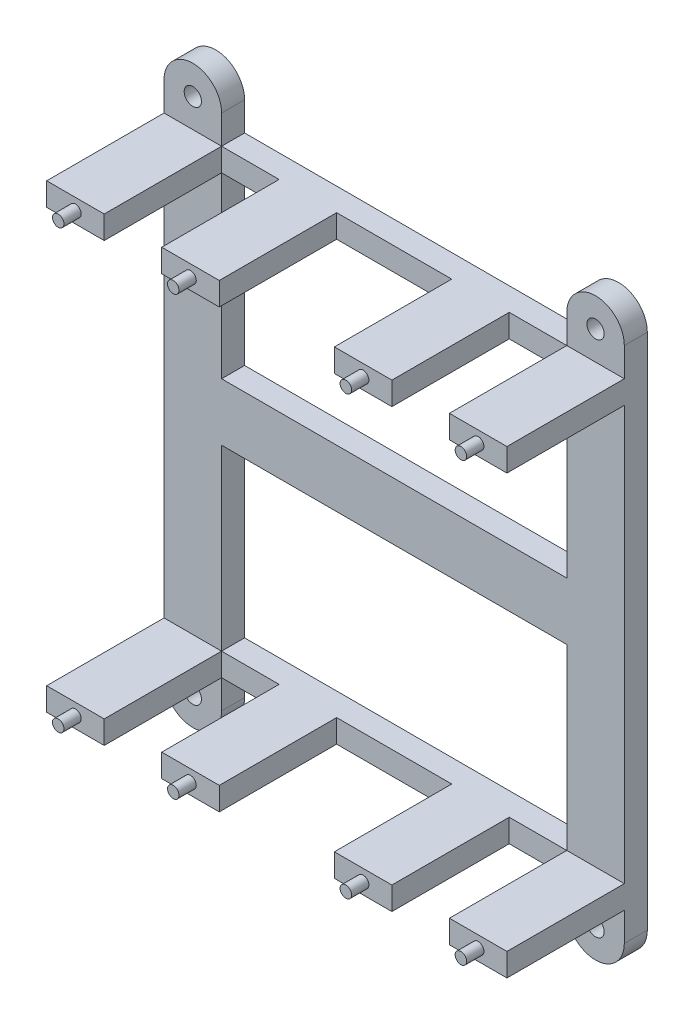
SolidWorks part; units mm, degrees
ref_plane "Alzado" through (0, 0, 0) normal (0, 0, 1) x (1, 0, 0)
ref_plane "Planta" through (0, 0, 0) normal (0, 1, 0) x (1, 0, 0)
ref_plane "Vista lateral" through (0, 0, 0) normal (1, 0, 0) x (0, 0, -1)
sketch "Croquis1" plane through (0, 0, 0) normal (0, 0, 1) x (1, 0, 0)
  line L0 (-50.9465, -21.9298) -> (-50.9465, -17.9298) construction
  line L1 (-50.9465, 58.0702) -> (29.0535, 58.0702)
  line L2 (-50.9465, 58.0702) -> (-50.9465, -21.9298)
  line L3 (-50.9465, -21.9298) -> (29.0535, -21.9298)
  line L4 (29.0535, 58.0702) -> (29.0535, -21.9298)
  line L5 (-50.9465, 58.0702) -> (-50.9465, 54.0702) construction
  line L6 (29.0535, -21.9298) -> (19.0535, -21.9298) construction
  line L7 (-50.9465, -17.9298) -> (29.0535, -17.9298)
  line L8 (-50.9465, -17.9298) -> (-50.9465, -21.9298)
  line L9 (-50.9465, -21.9298) -> (29.0535, -21.9298)
  line L10 (29.0535, -17.9298) -> (29.0535, -21.9298)
  line L11 (-50.9465, 54.0702) -> (29.0535, 54.0702)
  line L12 (-50.9465, 54.0702) -> (-50.9465, 58.0702)
  line L13 (-50.9465, 58.0702) -> (29.0535, 58.0702)
  line L14 (29.0535, 54.0702) -> (29.0535, 58.0702)
  line L15 (-50.9465, -21.9298) -> (-40.9465, -21.9298) construction
  line L16 (-50.9465, 18.0702) -> (29.0535, 18.0702) construction
  line L17 (29.0535, -21.9298) -> (19.0535, -21.9298)
  line L18 (29.0535, -21.9298) -> (29.0535, 58.0702)
  line L19 (29.0535, 58.0702) -> (19.0535, 58.0702)
  line L20 (19.0535, -21.9298) -> (19.0535, 58.0702)
  line L21 (-50.9465, 58.0702) -> (-40.9465, 58.0702)
  line L22 (-50.9465, 58.0702) -> (-50.9465, -21.9298)
  line L23 (-50.9465, -21.9298) -> (-40.9465, -21.9298)
  line L24 (-40.9465, 58.0702) -> (-40.9465, -21.9298)
  line L29 (19.0535, -21.9298) -> (9.5535, -21.9298) construction
  line L30 (29.0535, 18.0702) -> (29.0535, -6.4298) construction
  line L31 (29.0535, 18.0702) -> (29.0535, 42.5702) construction
  line L32 (29.0535, 42.5702) -> (-50.9465, 42.5702) construction
  line L33 (29.0535, -6.4298) -> (-50.9465, -6.4298) construction
  line L34 (29.0535, -6.4298) -> (26.0535, -6.4298) construction
  line L35 (-50.9465, 18.0702) -> (-50.9465, 43.0702) construction
  line L36 (-50.9465, 18.0702) -> (-50.9465, -6.9298) construction
  line L37 (-50.9465, 18.0702) -> (-50.9465, 49.0702) construction
  line L38 (-50.9465, 18.0702) -> (-50.9465, -12.9298) construction
  line L39 (-50.9465, 49.0702) -> (29.0535, 49.0702) construction
  line L40 (-50.9465, -12.9298) -> (29.0535, -12.9298) construction
  line L41 (9.5535, -21.9298) -> (9.5535, 58.0702) construction
  line L42 (9.5535, -12.9298) -> (-47.4465, -12.9298) construction
  line L43 (-47.4465, -21.9298) -> (-47.4465, 58.0702) construction
  line L44 (26.0535, -21.9298) -> (26.0535, 58.0702) construction
  line L45 (-50.9465, 43.0702) -> (29.0535, 43.0702) construction
  line L46 (-50.9465, -6.9298) -> (29.0535, -6.9298) construction
  line L47 (26.0535, -6.4298) -> (-31.9465, -6.4298) construction
  line L48 (-40.9465, 58.0702) -> (-40.9465, 68.0702) construction
  line L49 (-40.9465, -21.9298) -> (-40.9465, -31.9298) construction
  line L50 (-50.9465, -21.9298) -> (-40.9465, -31.9298) construction
  line L51 (-50.9465, -21.9298) -> (-40.9465, -21.9298)
  line L52 (-50.9465, -21.9298) -> (-50.9465, -31.9298)
  line L53 (-50.9465, -31.9298) -> (-40.9465, -31.9298)
  line L54 (-40.9465, -21.9298) -> (-40.9465, -31.9298)
  line L55 (19.0535, -21.9298) -> (29.0535, -21.9298)
  line L56 (19.0535, -21.9298) -> (19.0535, -31.9298)
  line L57 (19.0535, -31.9298) -> (29.0535, -31.9298)
  line L58 (29.0535, -21.9298) -> (29.0535, -31.9298)
  line L59 (-50.9465, 58.0702) -> (-40.9465, 58.0702)
  line L60 (-50.9465, 58.0702) -> (-50.9465, 68.0702)
  line L61 (-50.9465, 68.0702) -> (-40.9465, 68.0702)
  line L62 (-40.9465, 58.0702) -> (-40.9465, 68.0702)
  line L63 (19.0535, 58.0702) -> (29.0535, 58.0702)
  line L64 (19.0535, 58.0702) -> (19.0535, 68.0702)
  line L65 (19.0535, 68.0702) -> (29.0535, 68.0702)
  line L66 (29.0535, 58.0702) -> (29.0535, 68.0702)
  line L67 (-50.9465, -31.9298) -> (-40.9465, -21.9298) construction
  line L68 (19.0535, -21.9298) -> (29.0535, -31.9298) construction
  line L69 (19.0535, -31.9298) -> (29.0535, -21.9298) construction
  line L70 (19.0535, 68.0702) -> (29.0535, 58.0702) construction
  line L71 (29.0535, 68.0702) -> (19.0535, 58.0702) construction
  line L72 (-50.9465, 58.0702) -> (-40.9465, 68.0702) construction
  line L73 (-40.9465, 58.0702) -> (-50.9465, 68.0702) construction
  line L74 (-10.9465, 58.0702) -> (-10.9465, -21.9298)
  line L75 (-30.9465, 58.0702) -> (-30.9465, -21.9298)
  line L76 (9.0535, 58.0702) -> (9.0535, -21.9298)
  line L77 (-20.9465, 58.0702) -> (-20.9465, -21.9298)
  line L78 (-0.9465, 58.0702) -> (-0.9465, -21.9298)
  line L79 (-50.9465, 13.0702) -> (29.0535, 13.0702)
  line L80 (-50.9465, 23.0702) -> (29.0535, 23.0702)
  line L82 (-50.9465, 13.0702) -> (29.0535, 13.0702)
  line L83 (-50.9465, 13.0702) -> (-50.9465, 23.0702)
  line L84 (-50.9465, 23.0702) -> (29.0535, 23.0702)
  line L85 (29.0535, 13.0702) -> (29.0535, 23.0702)
  line L86 (-50.9465, -21.9298) -> (29.0535, -21.9298)
  line L87 (-50.9465, -21.9298) -> (-50.9465, -17.9298)
  line L88 (-50.9465, -17.9298) -> (29.0535, -17.9298)
  line L89 (29.0535, -21.9298) -> (29.0535, -17.9298)
  line L90 (-50.9465, 54.0702) -> (29.0535, 54.0702)
  line L91 (-50.9465, 54.0702) -> (-50.9465, 58.0702)
  line L92 (-50.9465, 58.0702) -> (29.0535, 58.0702)
  line L93 (29.0535, 54.0702) -> (29.0535, 58.0702)
  circle A0 centre (9.5535, -12.9298) radius 3.5
  circle A1 centre (9.5535, 49.0702) radius 3.5
  circle A2 centre (9.5535, 49.0702) radius 1.5
  circle A3 centre (9.5535, -12.9298) radius 1.5
  circle A4 centre (9.5535, 49.0702) radius 2.2
  circle A5 centre (9.5535, -12.9298) radius 2.2
  circle A12 centre (26.0535, 42.5702) radius 3
  circle A13 centre (26.0535, -6.4298) radius 3
  circle A14 centre (-47.4465, 43.0702) radius 3.5
  circle A15 centre (-47.4465, 43.0702) radius 2.2
  circle A16 centre (-47.4465, 43.0702) radius 1.5
  circle A17 centre (-47.4465, -6.9298) radius 3.5
  circle A18 centre (-47.4465, -6.9298) radius 2.2
  circle A19 centre (-47.4465, -6.9298) radius 1.5
  circle A20 centre (26.0535, -6.4298) radius 1.25
  circle A21 centre (26.0535, 42.5702) radius 1.25
  circle A22 centre (-31.9465, -6.4298) radius 3
  circle A23 centre (-31.9465, -6.4298) radius 1.25
  circle A24 centre (-31.9465, 42.5702) radius 3
  circle A25 centre (-31.9465, 42.5702) radius 1.25
  circle A26 centre (-45.9465, 63.0702) radius 1.5
  circle A27 centre (24.0535, 63.0702) radius 1.5
  circle A28 centre (24.0535, -26.9298) radius 1.5
  circle A29 centre (-45.9465, -26.9298) radius 1.5
  dimension "D15" = 57
  dimension "D16" = 58
  dimension "D19" = 20
  dimension "D1" = 80
  dimension "D2" = 80
  dimension "D3" = 4
  dimension "D4" = 4
  dimension "D5" = 10
  dimension "D6" = 10
  dimension "D7" = 9.5
  dimension "D8" = 24.5
  dimension "D9" = 24.5
  dimension "D10" = 3
  dimension "D11" = 25
  dimension "D12" = 25
  dimension "D13" = 31
  dimension "D14" = 31
  dimension "D20" = 20
  dimension "D21" = 10
  dimension "D22" = 10
  dimension "D23" = 5
  dimension "D24" = 5
extrude "Saliente-Extruir5" add sketch "Croquis1" along normal blind 4 contours L1 L62 L61 L60 A26 | L13 L66 L65 L64 A27 | L58 L9 L56 L57 A28 | L54 L3 L52 L53 A29 | L24 L7 L2 L3 | L75 L7 L24 L9 | L77 L7 L75 L3 | L7 L77 L9 L74 | L78 L7 L74 L3 | L7 L78 L9 L76 | L7 L76 L9 L20 | L20 L9 L4 L7 | A13 A20 | A20 | L4 A13 L18 L79 L20 L7 | L22 A17 L2 L7 L24 L79 | A17 A18 | A18 A19 | A19 | L80 L22 L79 L24 | L80 L24 L79 L75 | L80 L75 L79 L77 | L80 L77 L79 L74 | L80 L74 L79 L78 | L80 L78 L79 L76 | L80 L76 L79 L20 | L80 L20 L79 L18 | L2 A14 L22 L80 L24 L11 | L24 L1 L2 L11 | A14 A15 | A15 A16 | A16 | L75 L13 L24 L11 | L77 L1 L75 L11 | L13 L77 L11 L74 | L78 L1 L74 L11 | L13 L78 L11 L76 | L13 L76 L11 L20 | L20 L11 L4 L13 | L18 A12 L4 L11 L20 L80 | A12 A21 | A21 region at (-50.8051, 63.0702, 0) region at (-45.9465, 56.0702, 0) region at (-35.9465, 56.0702, 0) region at (-47.4465, 46.4712, 0) region at (-45.7339, 37.9323, 0) region at (-25.9465, 56.0702, 0) region at (-15.9465, 56.0702, 0) region at (-35.9465, 18.0702, 0) region at (-45.9465, 18.0702, 0) region at (-5.9465, 56.0702, 0) region at (-47.4465, -3.5288, 0) region at (-45.7339, -1.792, 0) region at (-25.9465, 18.0702, 0) region at (4.0535, 56.0702, 0) region at (-15.9465, 18.0702, 0) region at (-45.9465, -19.9298, 0) region at (-35.9465, -19.9298, 0) region at (14.0535, 56.0702, 0) region at (-5.9465, 18.0702, 0) region at (-25.9465, -19.9298, 0) region at (-41.0879, -26.9298, 0) region at (19.1949, 63.0702, 0) region at (24.0535, 56.0702, 0) region at (4.0535, 18.0702, 0) region at (-15.9465, -19.9298, 0) region at (23.1383, 42.5702, 0) region at (23.8528, 38.1687, 0) region at (14.0535, 18.0702, 0) region at (-5.9465, -19.9298, 0) region at (24.0535, 18.0702, 0) region at (4.0535, -19.9298, 0) region at (23.1383, -6.4298, 0) region at (23.8528, -2.0284, 0) region at (14.0535, -19.9298, 0) region at (24.0535, -19.9298, 0) region at (24.0535, -22.0712, 0) region at (-49.5843, 43.0702, 0) region at (-47.4465, 43.0702, 0) region at (-49.5843, -6.9298, 0) region at (-47.4465, -6.9298, 0) region at (26.0535, -6.4298, 0) region at (26.0535, 42.5702, 0)
extrude "Saliente-Extruir6" add sketch "Croquis1<6>" along normal blind 20.4 from surface contours L24 L1 L2 L11 | L77 L1 L75 L11 | L20 L11 L4 L13 | L13 L78 L11 L76 | L24 L7 L2 L3 | L77 L7 L75 L3 | L7 L78 L9 L76 | L20 L9 L4 L7 region at (-45.9465, 56.0702, 0) region at (-25.9465, 56.0702, 0) region at (4.0535, 56.0702, 0) region at (-45.9465, -19.9298, 0) region at (-25.9465, -19.9298, 0) region at (24.0535, 56.0702, 0) region at (4.0535, -19.9298, 0) region at (24.0535, -19.9298, 0) starting at face at (-10.9465, -2.4298, 4)
sketch "Croquis1<6>" plane through (0, 0, 0) normal (0, 0, 1) x (1, 0, 0) same geometry as "Croquis1"
extrude "Saliente-Extruir7" add sketch "Croquis1<7>" along normal blind 4 from surface contours L24 L1 L2 L11 | L75 L13 L24 L11 | L13 L77 L11 L74 | L78 L1 L74 L11 | L13 L78 L11 L76 | L77 L1 L75 L11 | L13 L76 L11 L20 | L18 A12 L4 L11 L20 L80 | L2 A14 L22 L80 L24 L11 | A24 L75 L11 L24 L80 | A14 A15 | A15 A16 | A16 | A12 A21 | A21 | L20 L11 L4 L13 | A25 L75 A24 | L75 A25 | A25 L75 A24 | L75 A25 | A24 L75 L80 L77 L11 | L77 L80 L74 L11 | L74 L80 L78 L11 | A1 L76 L11 L78 L80 | A4 L76 A1 | L76 A4 A2 | L76 A2 | L76 A2 | L76 A4 A2 | A4 L76 A1 | A1 L76 L80 L20 L11 | L80 L20 L79 L18 | L80 L76 L79 L20 | L80 L78 L79 L76 | L80 L74 L79 L78 | L80 L77 L79 L74 | L80 L75 L79 L77 | L80 L24 L79 L75 | L80 L22 L79 L24 | A22 L75 L79 L24 L7 | A22 L75 L7 L77 L79 | L79 L77 L7 L74 | L79 L74 L7 L78 | A0 L76 L79 L78 L7 | A0 L76 L7 L20 L79 | L22 A17 L2 L7 L24 L79 | A17 A18 | A18 A19 | A19 | A23 L75 A22 | L75 A23 | L75 A23 | A23 L75 A22 | A13 A20 | A20 | L76 A3 | L76 A3 | L76 A5 A3 | A5 L76 A0 | L76 A5 A3 | A5 L76 A0 | L20 L9 L4 L7 | L7 L76 L9 L20 | L7 L78 L9 L76 | L78 L7 L74 L3 | L7 L77 L9 L74 | L77 L7 L75 L3 | L75 L7 L24 L9 | L24 L7 L2 L3 | L4 A13 L18 L79 L20 L7 region at (-45.9465, 56.0702, 0) region at (-35.9465, 56.0702, 0) region at (-47.4465, 46.4712, 0) region at (-45.7339, 37.9323, 0) region at (-25.9465, 56.0702, 0) region at (-36.1707, 38.294, 0) region at (-15.9465, 56.0702, 0) region at (-25.8325, 38.4608, 0) region at (-35.9465, 18.0702, 0) region at (-45.9465, 18.0702, 0) region at (-5.9465, 56.0702, 0) region at (-15.9465, 38.5702, 0) region at (-30.0948, 42.5702, 0) region at (-31.0186, 44.3594, 0) region at (-36.1707, -2.1536, 0) region at (-47.4465, -3.5288, 0) region at (-45.7339, -1.792, 0) region at (-25.9465, 18.0702, 0) region at (4.0535, 56.0702, 0) region at (-5.9465, 38.5702, 0) region at (-15.9465, 18.0702, 0) region at (-30.8456, 42.5702, 0) region at (-32.007, 42.5702, 0) region at (-45.9465, -19.9298, 0) region at (-35.9465, -19.9298, 0) region at (-25.8325, -2.3205, 0) region at (14.0535, 56.0702, 0) region at (3.8532, 38.008, 0) region at (-5.9465, 18.0702, 0) region at (-15.9465, -2.4298, 0) region at (-25.9465, -19.9298, 0) region at (-30.0948, -6.4298, 0) region at (-31.0186, -4.6406, 0) region at (24.0535, 56.0702, 0) region at (14.3131, 37.7394, 0) region at (4.0535, 18.0702, 0) region at (-5.9465, -2.4298, 0) region at (-15.9465, -19.9298, 0) region at (-30.8456, -6.4298, 0) region at (-32.007, -6.4298, 0) region at (23.1383, 42.5702, 0) region at (23.8528, 38.1687, 0) region at (11.792, 51.655, 0) region at (8.978, 51.8734, 0) region at (3.8532, -1.8676, 0) region at (14.0535, 18.0702, 0) region at (-5.9465, -19.9298, 0) region at (24.0535, 18.0702, 0) region at (10.8889, 50.7531, 0) region at (9.0074, 50.8485, 0) region at (4.0535, -19.9298, 0) region at (14.3131, -1.599, 0) region at (23.1383, -6.4298, 0) region at (23.8528, -2.0284, 0) region at (9.9301, 49.0702, 0) region at (8.6393, 49.0702, 0) region at (14.0535, -19.9298, 0) region at (11.792, -10.345, 0) region at (8.978, -10.1266, 0) region at (24.0535, -19.9298, 0)
sketch "Croquis1<7>" plane through (0, 0, 0) normal (0, 0, 1) x (1, 0, 0) same geometry as "Croquis1"
extrude "Saliente-Extruir9" add sketch "Croquis1<10>" along normal blind 4 from surface contours A24 | A12 | A13 | A22 starting at face at (-10.9465, 18.0702, 28.4)
sketch "Croquis1<10>" plane through (0, 0, 0) normal (0, 0, 1) x (1, 0, 0) same geometry as "Croquis1"
extrude "Saliente-Extruir10" add sketch "Croquis1<11>" along normal blind 14 from surface contours A14 | A17 | A0 | A1 starting at face at (-34.9465, -6.4298, 28.4)
sketch "Croquis1<11>" plane through (0, 0, 0) normal (0, 0, 1) x (1, 0, 0) same geometry as "Croquis1"
extrude "Cortar-Extruir1" cut sketch "Croquis1<12>" against normal blind 14 and the other way blind 14 from surface contours A19 | A23 | A3 | A20 | A21 | A2 | A25 | A16 starting at face at (6.0535, 49.0702, 28.4)
sketch "Croquis1<12>" plane through (0, 0, 0) normal (0, 0, 1) x (1, 0, 0) same geometry as "Croquis1"
extrude "Cortar-Extruir2" cut sketch "Croquis1<13>" along normal blind 15 from surface contours A5 | A18 | A15 | A4 starting at face at (-33.1965, -6.4298, 24.4)
sketch "Croquis1<13>" plane through (0, 0, 0) normal (0, 0, 1) x (1, 0, 0) same geometry as "Croquis1"
fillet "Redondeo2" 2 edges at (-40.9465, 68.0702, 2) (-50.9465, 68.0702, 2) type full round first side face at (-40.9465, 63.0702, 2) second side face at (-50.9465, 18.0702, 12.96) middle face at (-45.9465, 68.0702, 2)
fillet "Redondeo3" 2 edges at (-50.9465, -31.9298, 2) (-40.9465, -31.9298, 2) type full round first side face at (-50.9465, 17.0702, 12.96) second side face at (-40.9465, -26.9298, 2) middle face at (-45.9465, -31.9298, 2)
fillet "Redondeo4" 2 edges at (19.0535, -31.9298, 2) (29.0535, -31.9298, 2) type full round first side face at (19.0535, -26.9298, 2) second side face at (29.0535, 18.0702, 12.96) middle face at (24.0535, -31.9298, 2)
fillet "Redondeo5" 2 edges at (19.0535, 68.0702, 2) (29.0535, 68.0702, 2) type full round first side face at (19.0535, 63.0702, 2) second side face at (29.0535, 19.0702, 12.96) middle face at (24.0535, 68.0702, 2)
sketch "Croquis2" plane through (0, 0, 0) normal (0, 0, 1) x (1, 0, 0)
  line L0 (-50.9465, -21.9298) -> (-50.9465, -17.9298) construction
  line L1 (-50.9465, 58.0702) -> (29.0535, 58.0702)
  line L2 (-50.9465, 58.0702) -> (-50.9465, -21.9298)
  line L3 (-50.9465, -21.9298) -> (29.0535, -21.9298)
  line L4 (29.0535, 58.0702) -> (29.0535, -21.9298)
  line L5 (-50.9465, 58.0702) -> (-50.9465, 54.0702) construction
  line L6 (29.0535, -21.9298) -> (19.0535, -21.9298) construction
  line L7 (-50.9465, -17.9298) -> (29.0535, -17.9298)
  line L8 (-50.9465, -17.9298) -> (-50.9465, -21.9298)
  line L9 (-50.9465, -21.9298) -> (29.0535, -21.9298)
  line L10 (29.0535, -17.9298) -> (29.0535, -21.9298)
  line L11 (-50.9465, 54.0702) -> (29.0535, 54.0702)
  line L12 (-50.9465, 54.0702) -> (-50.9465, 58.0702)
  line L13 (-50.9465, 58.0702) -> (29.0535, 58.0702)
  line L14 (29.0535, 54.0702) -> (29.0535, 58.0702)
  line L15 (-50.9465, -21.9298) -> (-40.9465, -21.9298) construction
  line L16 (-50.9465, 18.0702) -> (29.0535, 18.0702) construction
  line L17 (29.0535, -21.9298) -> (19.0535, -21.9298)
  line L18 (29.0535, -21.9298) -> (29.0535, 58.0702)
  line L19 (29.0535, 58.0702) -> (19.0535, 58.0702)
  line L20 (19.0535, -21.9298) -> (19.0535, 58.0702)
  line L21 (-50.9465, 58.0702) -> (-40.9465, 58.0702)
  line L22 (-50.9465, 58.0702) -> (-50.9465, -21.9298)
  line L23 (-50.9465, -21.9298) -> (-40.9465, -21.9298)
  line L24 (-40.9465, 58.0702) -> (-40.9465, -21.9298)
  line L29 (19.0535, -21.9298) -> (9.5535, -21.9298) construction
  line L30 (29.0535, 18.0702) -> (29.0535, -6.4298) construction
  line L31 (29.0535, 18.0702) -> (29.0535, 42.5702) construction
  line L32 (29.0535, 42.5702) -> (-50.9465, 42.5702) construction
  line L33 (29.0535, -6.4298) -> (-50.9465, -6.4298) construction
  line L34 (29.0535, -6.4298) -> (26.0535, -6.4298) construction
  line L35 (-50.9465, 18.0702) -> (-50.9465, 43.0702) construction
  line L36 (-50.9465, 18.0702) -> (-50.9465, -6.9298) construction
  line L37 (-50.9465, 18.0702) -> (-50.9465, 49.0702) construction
  line L38 (-50.9465, 18.0702) -> (-50.9465, -12.9298) construction
  line L39 (-50.9465, 49.0702) -> (29.0535, 49.0702) construction
  line L40 (-50.9465, -12.9298) -> (29.0535, -12.9298) construction
  line L41 (9.5535, -21.9298) -> (9.5535, 58.0702) construction
  line L42 (9.5535, -12.9298) -> (-47.4465, -12.9298) construction
  line L43 (-47.4465, -21.9298) -> (-47.4465, 58.0702) construction
  line L44 (26.0535, -21.9298) -> (26.0535, 58.0702) construction
  line L45 (-50.9465, 43.0702) -> (29.0535, 43.0702) construction
  line L46 (-50.9465, -6.9298) -> (29.0535, -6.9298) construction
  line L47 (26.0535, -6.4298) -> (-31.9465, -6.4298) construction
  line L48 (-40.9465, 58.0702) -> (-40.9465, 68.0702) construction
  line L49 (-40.9465, -21.9298) -> (-40.9465, -31.9298) construction
  line L50 (-50.9465, -21.9298) -> (-40.9465, -31.9298) construction
  line L51 (-50.9465, -21.9298) -> (-40.9465, -21.9298)
  line L52 (-50.9465, -21.9298) -> (-50.9465, -31.9298)
  line L53 (-50.9465, -31.9298) -> (-40.9465, -31.9298)
  line L54 (-40.9465, -21.9298) -> (-40.9465, -31.9298)
  line L55 (19.0535, -21.9298) -> (29.0535, -21.9298)
  line L56 (19.0535, -21.9298) -> (19.0535, -31.9298)
  line L57 (19.0535, -31.9298) -> (29.0535, -31.9298)
  line L58 (29.0535, -21.9298) -> (29.0535, -31.9298)
  line L59 (-50.9465, 58.0702) -> (-40.9465, 58.0702)
  line L60 (-50.9465, 58.0702) -> (-50.9465, 68.0702)
  line L61 (-50.9465, 68.0702) -> (-40.9465, 68.0702)
  line L62 (-40.9465, 58.0702) -> (-40.9465, 68.0702)
  line L63 (19.0535, 58.0702) -> (29.0535, 58.0702)
  line L64 (19.0535, 58.0702) -> (19.0535, 68.0702)
  line L65 (19.0535, 68.0702) -> (29.0535, 68.0702)
  line L66 (29.0535, 58.0702) -> (29.0535, 68.0702)
  line L67 (-50.9465, -31.9298) -> (-40.9465, -21.9298) construction
  line L68 (19.0535, -21.9298) -> (29.0535, -31.9298) construction
  line L69 (19.0535, -31.9298) -> (29.0535, -21.9298) construction
  line L70 (19.0535, 68.0702) -> (29.0535, 58.0702) construction
  line L71 (29.0535, 68.0702) -> (19.0535, 58.0702) construction
  line L72 (-50.9465, 58.0702) -> (-40.9465, 68.0702) construction
  line L73 (-40.9465, 58.0702) -> (-50.9465, 68.0702) construction
  line L74 (-10.9465, 58.0702) -> (-10.9465, -21.9298)
  line L75 (-30.9465, 58.0702) -> (-30.9465, -21.9298)
  line L76 (9.0535, 58.0702) -> (9.0535, -21.9298)
  line L77 (-20.9465, 58.0702) -> (-20.9465, -21.9298)
  line L78 (-0.9465, 58.0702) -> (-0.9465, -21.9298)
  line L79 (-50.9465, 13.0702) -> (29.0535, 13.0702)
  line L80 (-50.9465, 23.0702) -> (29.0535, 23.0702)
  line L82 (-50.9465, 13.0702) -> (29.0535, 13.0702)
  line L83 (-50.9465, 13.0702) -> (-50.9465, 23.0702)
  line L84 (-50.9465, 23.0702) -> (29.0535, 23.0702)
  line L85 (29.0535, 13.0702) -> (29.0535, 23.0702)
  line L86 (-50.9465, -21.9298) -> (29.0535, -21.9298)
  line L87 (-50.9465, -21.9298) -> (-50.9465, -17.9298)
  line L88 (-50.9465, -17.9298) -> (29.0535, -17.9298)
  line L89 (29.0535, -21.9298) -> (29.0535, -17.9298)
  line L90 (-50.9465, 54.0702) -> (29.0535, 54.0702)
  line L91 (-50.9465, 54.0702) -> (-50.9465, 58.0702)
  line L92 (-50.9465, 58.0702) -> (29.0535, 58.0702)
  line L93 (29.0535, 54.0702) -> (29.0535, 58.0702)
  circle A0 centre (9.5535, -12.9298) radius 3.5
  circle A1 centre (9.5535, 49.0702) radius 3.5
  circle A2 centre (9.5535, 49.0702) radius 1.5
  circle A3 centre (9.5535, -12.9298) radius 1.5
  circle A4 centre (9.5535, 49.0702) radius 2.2
  circle A5 centre (9.5535, -12.9298) radius 2.2
  circle A12 centre (26.0535, 42.5702) radius 3
  circle A13 centre (26.0535, -6.4298) radius 3
  circle A14 centre (-47.4465, 43.0702) radius 3.5
  circle A15 centre (-47.4465, 43.0702) radius 2.2
  circle A16 centre (-47.4465, 43.0702) radius 1.5
  circle A17 centre (-47.4465, -6.9298) radius 3.5
  circle A18 centre (-47.4465, -6.9298) radius 2.2
  circle A19 centre (-47.4465, -6.9298) radius 1.5
  circle A20 centre (26.0535, -6.4298) radius 1.25
  circle A21 centre (26.0535, 42.5702) radius 1.25
  circle A22 centre (-31.9465, -6.4298) radius 3
  circle A23 centre (-31.9465, -6.4298) radius 1.25
  circle A24 centre (-31.9465, 42.5702) radius 3
  circle A25 centre (-31.9465, 42.5702) radius 1.25
  circle A26 centre (-45.9465, 63.0702) radius 1.5
  circle A27 centre (24.0535, 63.0702) radius 1.5
  circle A28 centre (24.0535, -26.9298) radius 1.5
  circle A29 centre (-45.9465, -26.9298) radius 1.5
  ellipse E0 centre (-10.9465, 18.0702) end of major axis (-40.9465, 18.0702) minor radius 25
  ellipse E1 centre (-10.9465, 18.0702) end of major axis (-10.9465, -17.9298) minor radius 20
  dimension "D15" = 57
  dimension "D16" = 58
  dimension "D19" = 20
  dimension "D1" = 80
  dimension "D2" = 80
  dimension "D3" = 4
  dimension "D4" = 4
  dimension "D5" = 10
  dimension "D6" = 10
  dimension "D7" = 9.5
  dimension "D8" = 24.5
  dimension "D9" = 24.5
  dimension "D10" = 3
  dimension "D11" = 25
  dimension "D12" = 25
  dimension "D13" = 31
  dimension "D14" = 31
  dimension "D20" = 20
  dimension "D21" = 10
  dimension "D22" = 10
  dimension "D23" = 5
  dimension "D24" = 5
fillet "Redondeo6" radius 4 1 edges at (-10.9465, -21.9298, 28.4) type face fillet first side face at (-10.9465, -21.9298, 11.65) second side face at (6.0535, 49.0702, 28.4)
fillet "Redondeo7" radius 4 1 edges at (-10.9465, 58.0702, 28.4) type face fillet first side face at (-10.9465, 58.0702, 11.65) second side face at (6.0535, 49.0702, 28.4)
extrude "Cortar-Extruir6" cut sketch "Croquis2" against normal blind 8 from surface contours E1 | E0 starting at face at (6.0535, 49.0702, 28.4)
sketch "Croquis3" plane through (0, -21.9298, 0) normal (0, -1, 0) x (1, 0, 0)
  line L0 (-43.9465, 42.4) -> (-50.9465, 42.4) construction
  line L1 (29.0535, 24.4) -> (-50.9465, 24.4)
  line L2 (29.0535, 24.4) -> (29.0535, 42.4)
  line L3 (29.0535, 42.4) -> (-50.9465, 42.4)
  line L4 (-50.9465, 24.4) -> (-50.9465, 42.4)
extrude "Cortar-Extruir7" cut sketch "Croquis3" against normal blind 80
sketch "Croquis4" plane through (0, 0, 24.4) normal (0, 0, 1) x (1, 0, 0)
  line L0 (29.0535, 56.0702) -> (-50.9465, 56.0702) construction
  line L1 (29.0535, 58.0702) -> (19.0535, 58.0702)
  line L2 (29.0535, 58.0702) -> (29.0535, 54.0702)
  line L3 (29.0535, 54.0702) -> (19.0535, 54.0702)
  line L4 (19.0535, 58.0702) -> (19.0535, 54.0702)
  line L5 (9.0535, 58.0702) -> (-0.9465, 58.0702)
  line L6 (9.0535, 58.0702) -> (9.0535, 54.0702)
  line L7 (9.0535, 54.0702) -> (-0.9465, 54.0702)
  line L8 (-0.9465, 58.0702) -> (-0.9465, 54.0702)
  line L9 (-20.9465, 58.0702) -> (-30.9465, 58.0702)
  line L10 (-20.9465, 58.0702) -> (-20.9465, 54.0702)
  line L11 (-20.9465, 54.0702) -> (-30.9465, 54.0702)
  line L12 (-30.9465, 58.0702) -> (-30.9465, 54.0702)
  line L13 (-40.9465, 58.0702) -> (-50.9465, 58.0702)
  line L14 (-40.9465, 58.0702) -> (-40.9465, 54.0702)
  line L15 (-40.9465, 54.0702) -> (-50.9465, 54.0702)
  line L16 (-50.9465, 58.0702) -> (-50.9465, 54.0702)
  line L17 (-40.9465, -17.9298) -> (-50.9465, -17.9298)
  line L18 (-40.9465, -17.9298) -> (-40.9465, -21.9298)
  line L19 (-40.9465, -21.9298) -> (-50.9465, -21.9298)
  line L20 (-50.9465, -17.9298) -> (-50.9465, -21.9298)
  line L21 (-30.9465, -17.9298) -> (-20.9465, -17.9298)
  line L22 (-30.9465, -17.9298) -> (-30.9465, -21.9298)
  line L23 (-30.9465, -21.9298) -> (-20.9465, -21.9298)
  line L24 (-20.9465, -17.9298) -> (-20.9465, -21.9298)
  line L25 (-0.9465, -17.9298) -> (9.0535, -17.9298)
  line L26 (-0.9465, -17.9298) -> (-0.9465, -21.9298)
  line L27 (-0.9465, -21.9298) -> (9.0535, -21.9298)
  line L28 (9.0535, -17.9298) -> (9.0535, -21.9298)
  line L29 (19.0535, -17.9298) -> (29.0535, -17.9298)
  line L34 (19.0535, -17.9298) -> (19.0535, -21.9298)
  line L35 (19.0535, -21.9298) -> (29.0535, -21.9298)
  line L36 (29.0535, -17.9298) -> (29.0535, -21.9298)
  line L37 (-50.9465, 56.0702) -> (-50.9465, -19.9298) construction
  line L38 (-50.9465, -19.9298) -> (29.0535, -19.9298) construction
  line L39 (29.0535, -19.9298) -> (24.0535, -21.9298) construction
  line L40 (24.0535, -21.9298) -> (24.0535, 58.0702) construction
  line L41 (24.0535, 58.0702) -> (4.0535, 58.0702) construction
  line L42 (4.0535, 58.0702) -> (4.0535, -21.9298) construction
  line L43 (4.0535, -21.9298) -> (-25.9465, -21.9298) construction
  line L44 (-25.9465, -21.9298) -> (-25.9465, 58.0702) construction
  line L45 (-25.9465, 58.0702) -> (-45.9465, 58.0702) construction
  line L46 (-45.9465, 58.0702) -> (-45.9465, -21.9298) construction
  circle A0 centre (24.0535, 56.0702) radius 1
  circle A1 centre (24.0535, -19.9298) radius 1
  circle A2 centre (4.0535, -19.9298) radius 1
  circle A3 centre (-25.9465, -19.9298) radius 1
  circle A4 centre (-45.9465, -19.9298) radius 1
  circle A5 centre (-25.9465, 56.0702) radius 1
  circle A6 centre (-45.9465, 56.0702) radius 1
  circle A7 centre (4.0535, 56.0702) radius 1
extrude "Saliente-Extruir11" add sketch "Croquis4" along normal blind 3 contours A0 | A5 | A6 | A4 | A3 | A2 | A1 | A7
